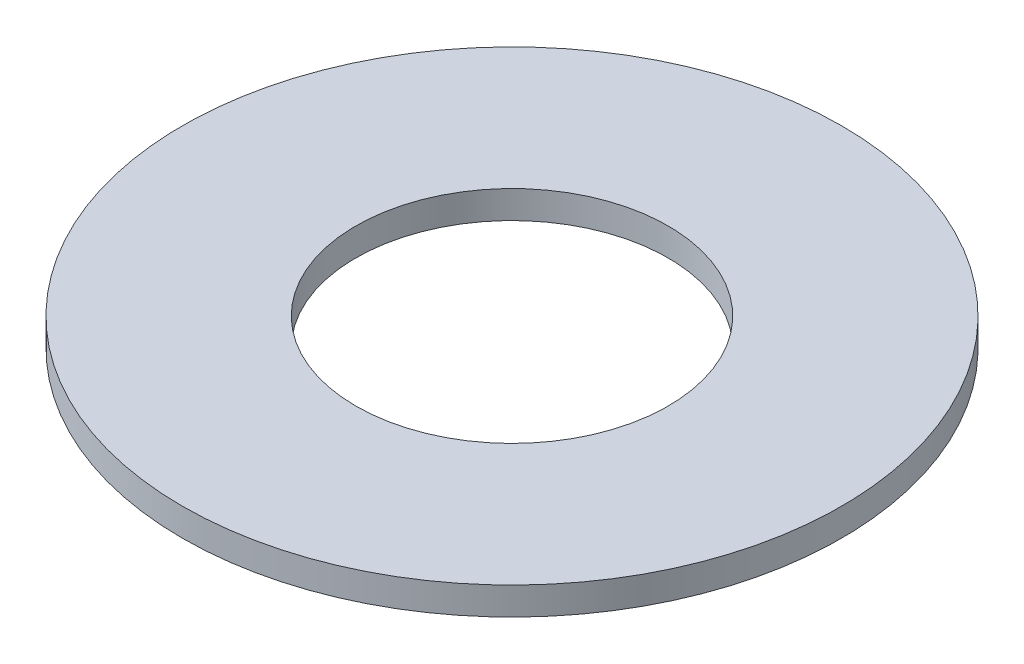
SolidWorks part; units mm, degrees
ref_plane "Front Plane" through (0, 0, 0) normal (0, 0, 1) x (1, 0, 0)
ref_plane "Top Plane" through (0, 0, 0) normal (0, 1, 0) x (1, 0, 0)
ref_plane "Right Plane" through (0, 0, 0) normal (1, 0, 0) x (0, 0, -1)
sketch "Sketch1" plane through (0, 0, 0) normal (0, 1, 0) x (1, 0, 0)
  circle A0 centre (0, 0) radius 47.5
  dimension "FLANGE_OD" = 95
extrude "Boss-Extrude1" add sketch "Sketch1" along normal blind 4
sketch "Sketch2" plane through (0, 0, 0) normal (0, 1, 0) x (1, 0, 0)
  circle A0 centre (0, 0) radius 22.5
  dimension "BORE_D" = 45
extrude "Cut-Extrude1" cut sketch "Sketch2" along normal through all
sketch "Sketch3" plane through (0, 4, 0) normal (0, 1, 0) x (1, 0, 0)
  circle A0 centre (0, 0) radius 15.9301 construction
  circle A1 centre (-15.9301, 0) radius 2.1973
  dimension "BOLT_D" = 4.3947
  dimension "BOLT_PCD" = 31.8602
extrude "Cut-Extrude2" cut sketch "Sketch3" against normal blind 3.4065 rebuild error yes
pattern_circular "CirPattern1" count 6 over 360 rebuild error yes
